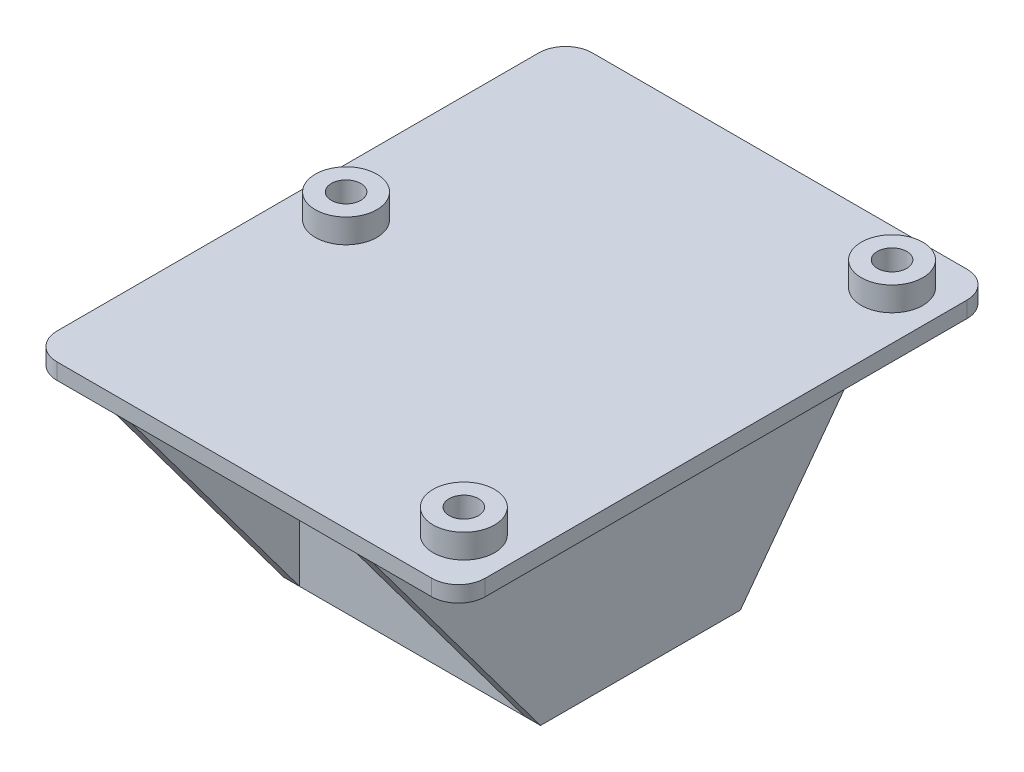
SolidWorks part; units mm, degrees
material "ABS"
ref_plane "Front Plane" through (0, 0, 0) normal (0, 0, 1) x (1, 0, 0)
ref_plane "Top Plane" through (0, 0, 0) normal (0, 1, 0) x (1, 0, 0)
ref_plane "Right Plane" through (0, 0, 0) normal (1, 0, 0) x (0, 0, -1)
sketch "Sketch1" plane through (0, 0, 0) normal (0, 1, 0) x (1, 0, 0)
  line L10 (-35, 50) -> (35, 50)
  line L11 (-40, 45) -> (-40, -45)
  line L12 (-35, -50) -> (35, -50)
  line L13 (40, 45) -> (40, -45)
  line L14 (-40, 50) -> (40, -50) construction
  line L15 (-40, -50) -> (40, 50) construction
  arc A0 (35, 50) -> (40, 45) centre (35, 45) cw
  arc A1 (35, -50) -> (40, -45) centre (35, -45) ccw
  arc A2 (-40, -45) -> (-35, -50) centre (-35, -45) ccw
  arc A3 (-35, 50) -> (-40, 45) centre (-35, 45) ccw
  point P0 (0, 0)
  dimension "D3" = 5
  dimension "D1" = 80
  dimension "D2" = 100
extrude "Boss-Extrude1" add sketch "Sketch1" along normal blind 3
sketch "Sketch2" plane through (0, 3, 0) normal (0, 1, 0) x (1, 0, 0)
  line L0 (-31, 0) -> (0, 0) construction
  line L1 (0, 0) -> (31, 0) construction
  line L2 (31, 40) -> (31, -40) construction
  line L4 (-31, 0) -> (-40, 0) construction
  line L5 (-40, 45) -> (-40, -45) construction
  line L6 (31, 0) -> (40, 0) construction
  line L7 (40, -45) -> (40, 45) construction
  circle A0 centre (-31, 0) radius 2.75
  circle A1 centre (31, 40) radius 2.75
  circle A2 centre (31, -40) radius 2.75
  dimension "D4" = 5.5
  dimension "D1" = 62
  dimension "D3" = 80
extrude "Cut-Extrude1" cut sketch "Sketch2" against normal through all
sketch "Sketch3" plane through (0, 3, 0) normal (0, 1, 0) x (1, 0, 0)
  circle A0 centre (31, -40) radius 2.75 construction
  circle A1 centre (-31, 0) radius 2.75 construction
  circle A2 centre (31, 40) radius 2.75 construction
  circle A3 centre (31, -40) radius 2.75
  circle A4 centre (-31, 0) radius 2.75
  circle A5 centre (31, 40) radius 2.75
  circle A6 centre (-31, 0) radius 5.75
  circle A7 centre (31, 40) radius 5.75
  circle A8 centre (31, -40) radius 5.75
  dimension "D1" = 3
extrude "Boss-Extrude3" add sketch "Sketch3<2>" along normal blind 4.5
sketch "Sketch3<2>" plane through (0, 3, 0) normal (0, 1, 0) x (1, 0, 0) same geometry as "Sketch3"
sketch "Sketch6" plane through (0, 3, 0) normal (0, 1, 0) x (1, 0, 0)
  line L0 (-36.4704, -29.7789) -> (28.5296, -49.7789)
  line L1 (-40, 45) -> (-40, -45) construction
  line L2 (-35, -50) -> (35, -50) construction
  line L3 (-40, 0) -> (40, 0) construction
  line L4 (40, -45) -> (40, 45) construction
  line L5 (-40, -25) -> (-40, -50)
  line L6 (-40, -50) -> (30, -50)
  line L7 (-40, 50) -> (30, 50)
  line L8 (-40, 25) -> (-40, 50)
  line L9 (-36.4704, 29.7789) -> (28.5296, 49.7789)
  arc A1 (-40, -25) -> (-36.4704, -29.7789) centre (-35, -25) ccw
  arc A2 (28.5296, -49.7789) -> (30, -50) centre (30, -45) ccw
  arc A3 (28.5296, 49.7789) -> (30, 50) centre (30, 45) cw
  arc A4 (-40, 25) -> (-36.4704, 29.7789) centre (-35, 25) cw
  dimension "D1" = 10
  dimension "D2" = 10
  dimension "D3" = 25
  dimension "D4" = 10
extrude "Boss-Extrude2" add sketch "Sketch3" along normal blind 4.5
sketch "Sketch7" plane through (0, 0, 0) normal (0, -1, 0) x (1, 0, 0)
  line L0 (21, 50) -> (24, 50)
  line L5 (-24, 50) -> (-21, 50)
  line L6 (-24, 50) -> (-24, -50)
  line L7 (-24, -50) -> (-21, -50)
  line L8 (24, 50) -> (24, -50)
  line L10 (21, -50) -> (21, -18.6667)
  line L11 (21, -18.6667) -> (-21, -18.6667)
  line L12 (-21, -50) -> (-21, -18.6667)
  line L14 (21, 50) -> (21, 18.6667)
  line L15 (21, 18.6667) -> (-21, 18.6667)
  line L16 (-21, 50) -> (-21, 18.6667)
  line L17 (-21, 15.6667) -> (21, 15.6667)
  line L18 (-21, 15.6667) -> (-21, -15.6667)
  line L19 (-21, -15.6667) -> (21, -15.6667)
  line L20 (21, 15.6667) -> (21, -15.6667)
  line L21 (21, -50) -> (24, -50)
  line L22 (-31, 0) -> (-24, 0) construction
  line L23 (31, -40) -> (24, -40) construction
  line L24 (-40, 50) -> (30, 50) construction
  point P22 (-24, 0)
  dimension "D1" = 3
  dimension "D2" = 3
  dimension "D3" = 3
  dimension "D4" = 42
extrude "Boss-Extrude4" add sketch "Sketch7" along normal blind 42
sketch "Sketch8" plane through (-21, 0, 0) normal (1, 0, 0) x (0, 0, -1)
  line L0 (-50, 0) -> (-18.6667, -42)
  line L1 (-18.6667, -42) -> (-50, -42)
  line L2 (-50, -42) -> (-50, 0)
  line L3 (18.6667, -42) -> (50, 0)
  line L4 (50, 0) -> (50, -42)
  line L5 (50, -42) -> (18.6667, -42)
extrude "Cut-Extrude2" cut sketch "Sketch8" against normal through all both and the other way through all
sketch "Sketch9" plane through (0, 0, 18.6667) normal (0, 0, 1) x (1, 0, 0)
  line L0 (0, -21) -> (-8.8388, -12.1612) construction
  line L1 (0, 0) -> (0, -21) construction
  line L2 (-21, -21) -> (0, -21) construction
  line L3 (-21, -42) -> (-21, 0) construction
  circle A0 centre (0, -21) radius 5
  circle A1 centre (-8.8388, -12.1612) radius 1.5
  circle A2 centre (-8.8388, -29.8388) radius 1.5
  circle A3 centre (8.8388, -29.8388) radius 1.5
  circle A4 centre (8.8388, -12.1612) radius 1.5
  point P8 (0, 0)
  point P11 (-9.9459, -13.4284)
  dimension "D2" = 10
  dimension "D3" = 3
  dimension "D1" = 12.5
  dimension "D4" = 45
extrude "Cut-Extrude3" cut sketch "Sketch9" against normal through all
